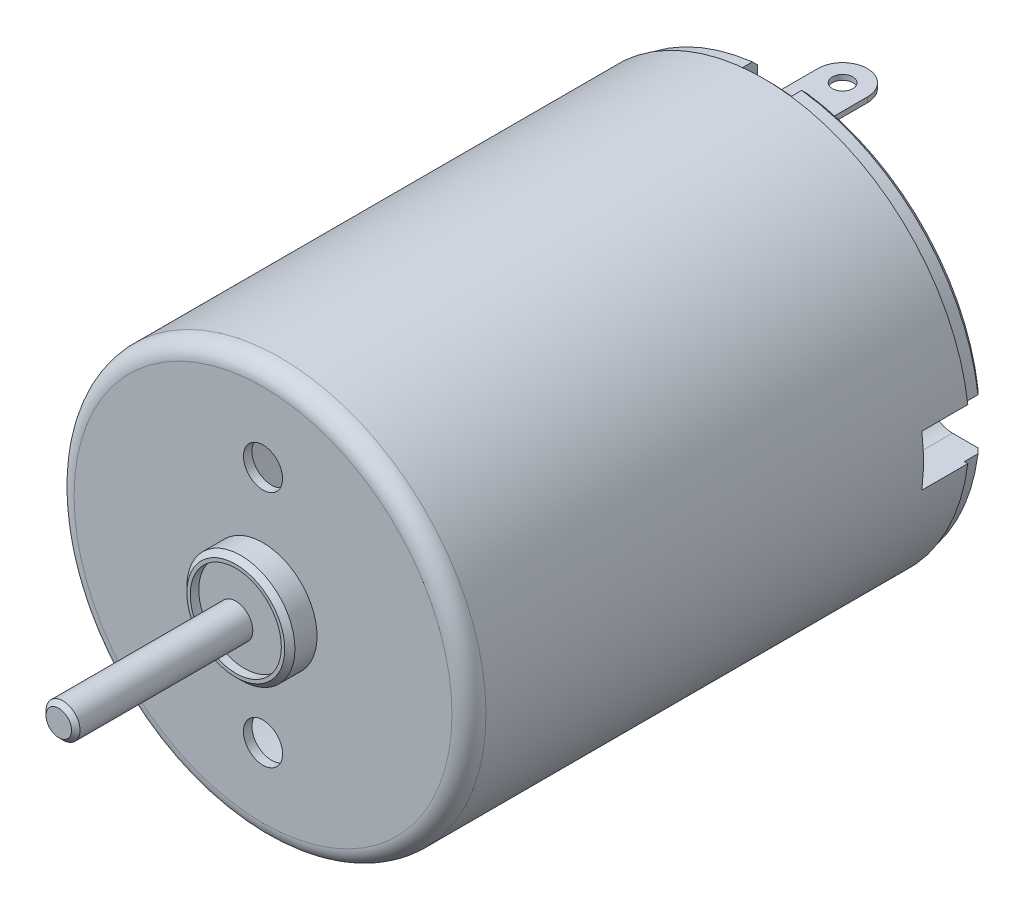
SolidWorks part; units mm, degrees
ref_plane "Front Plane" through (0, 0, 0) normal (0, 0, 1) x (1, 0, 0)
ref_plane "Top Plane" through (0, 0, 0) normal (0, 1, 0) x (1, 0, 0)
ref_plane "Right Plane" through (0, 0, 0) normal (1, 0, 0) x (0, 0, -1)
sketch "Sketch1" plane through (0, 0, 0) normal (0, 0, 1) x (1, 0, 0)
  circle A0 centre (0, 0) radius 12.1
  dimension "D1" = 24.2
extrude "Body" add sketch "Sketch1" along normal blind 30.5
sketch "Sketch2" plane through (0, 0, 30.5) normal (0, 0, 1) x (1, 0, 0)
  circle A0 centre (0, 0) radius 3.175
  dimension "D1" = 6.35
extrude "Boss-Extrude2" add sketch "Sketch2" along normal blind 1.6
sketch "Sketch3" plane through (0, 0, 32.1) normal (0, 0, 1) x (1, 0, 0)
  circle A0 centre (0, 0) radius 1
  dimension "D1" = 2
extrude "Shaft-front" add sketch "Sketch3" along normal offset from surface (10.4 mm away) 12 contours A0 up to face at (3.175, 0, 30.5) offset beyond the face yes
sketch "Sketch4" plane through (0, 0, 0) normal (0, 0, -1) x (-1, 0, 0)
  circle A0 centre (0, 0) radius 4.25
  dimension "D1" = 8.5
extrude "Boss-Extrude5" add sketch "Sketch4" along normal blind 2
sketch "Sketch5" plane through (0, 0, -2) normal (0, 0, -1) x (-1, 0, 0)
  circle A0 centre (0, 0) radius 1 construction
  circle A1 centre (0, 0) radius 1
extrude "Shaft-rear" add sketch "Sketch5" along normal offset from surface (0.5 mm away) 45 up to face at (1, 0, 42.5)
sketch "Sketch6" plane through (0, 0, 30.5) normal (0, 0, 1) x (1, 0, 0)
  line L0 (0, 7) -> (0, -7) construction
  circle A0 centre (0, 7) radius 1.15
  circle A1 centre (0, -7) radius 1.15
  dimension "D2" = 2.3
  dimension "D1" = 14
extrude "Cut-Extrude1" cut sketch "Sketch6" against normal offset from surface (28.5 mm away) 2 up to face at (-4.25, 0, 0)
sketch "Sketch7" plane through (0, 0, 0) normal (0, 0, -1) x (-1, 0, 0)
  line L0 (-6.45, 0) -> (6.45, 0) construction
  circle A0 centre (-6.45, 0) radius 1
  circle A1 centre (6.45, 0) radius 1
  dimension "D2" = 2
  dimension "D1" = 12.9
extrude "Cut-Extrude2" cut sketch "Sketch7" against normal offset from surface (28.5 mm away) 2 up to face at (1.15, 7, 30.5)
sketch "Sketch8" plane through (0, 0, -2) normal (0, 0, -1) x (-1, 0, 0)
  line L0 (3.75, 2) -> (3.75, -2)
  line L1 (-4.25, -5.1764) -> (-4.25, 5.307) construction
  circle A0 centre (0, 0) radius 4.25 construction
  circle A1 centre (0, 0) radius 4.25 construction
  arc A2 (3.75, -2) -> (3.75, 2) centre (0, 0) ccw
  dimension "D1" = 8
extrude "Cut-Extrude3" cut sketch "Sketch8" against normal up to surface (2 mm away) up to face at (5.45, 0, 0)
sketch "Sketch9" plane through (0, 0, 0) normal (0, 0, -1) x (-1, 0, 0)
  circle A0 centre (0, 0) radius 12.1 construction
  circle A1 centre (0, 0) radius 12.1
  circle A2 centre (0, 0) radius 11.9
  dimension "D1" = 23.8
extrude "Cut-Extrude4" cut sketch "Sketch9" against normal blind 1.1
chamfer "Chamfer1" distance 0.25 angle 45 2 edges at (1, 0, -2.5) (1, 0, 42.5)
sketch "Sketch10" plane through (0, 0, 0) normal (0, 0, -1) x (-1, 0, 0)
  line L0 (7.8477, -1.9) -> (4.9477, -1.9)
  line L2 (-1.45, -7.9432) -> (-1.45, -11.8113)
  line L4 (1.45, -7.9432) -> (1.45, -11.8113)
  line L5 (-4.9477, -1.9) -> (-7.8477, -1.9)
  line L6 (0, 0) -> (0, -12.9818) construction
  arc A0 (-7.8477, -1.9) -> (-1.45, -7.9432) centre (0, 0) ccw
  circle A1 centre (0, 0) radius 11.9
  circle A2 centre (0, 0) radius 11.9
  arc A3 (-4.9477, -1.9) -> (4.9477, -1.9) centre (0, 0) ccw
  arc A4 (1.45, -7.9432) -> (7.8477, -1.9) centre (0, 0) ccw
  circle M11 centre (0, 0) radius 11.9
  dimension "D3" = 2.9
  dimension "D4" = 5.3
  dimension "D2" = 2.9
  dimension "D5" = 1.9
  dimension "D1" = 0
extrude "Cut-Extrude5" cut sketch "Sketch10" against normal blind 0.9 contours L6 A3 L5 A0 L2 M11 | A3 L6 A2 L4 A4 L0 region at (-3.2233, -5.9985, 0) region at (3.2233, -5.9985, 0)
chamfer "Chamfer2" distance 0.3 angle 45 4 edges at (3.175, 0, 32.1) (-3.75, 0, -2) (4.25, 0, -2) (0, 11.9, 0)
fillet "Fillet1" radius 1 1 edges at (12.1, 0, 30.5)
mirror "Mirror1" about plane through (0, 0, 0) normal (0, 1, 0) of "Cut-Extrude5"
sketch "Sketch11" plane through (0, 0, 0) normal (0, 0, -1) x (-1, 0, 0)
  line L0 (-12.1, 0) -> (-10.0067, 0) construction
  line L1 (-12.0067, 1.5) -> (-10.0067, 1.5)
  line L2 (-12.0067, -1.5) -> (-10.0067, -1.5)
  circle A0 centre (0, 0) radius 12.1 construction
  arc A1 (-12.0067, 1.5) -> (-12.0067, -1.5) centre (0, 0) ccw
  arc A3 (-10.0067, -1.5) -> (-10.0067, 1.5) centre (-10.0067, 0) ccw
  dimension "D1" = 3
  dimension "D2" = 2
extrude "Cut-Extrude6" cut sketch "Sketch11" against normal blind 3.8
mirror "Mirror2" about plane through (0, 0, 0) normal (1, 0, 0) of "Cut-Extrude6"
sketch "Sketch12" plane through (0, 0, 0.9) normal (0, 0, -1) x (-1, 0, 0)
  line L0 (-1.45, -7.9432) -> (-1.45, -11.509) construction
  line L1 (-1.45, -9.25) -> (1.45, -9.25)
  line L2 (-1.45, -9.25) -> (-1.45, -9.55)
  line L3 (-1.45, -9.55) -> (1.45, -9.55)
  line L4 (1.45, -9.25) -> (1.45, -9.55)
  line L5 (1.45, -7.9432) -> (1.45, -11.509) construction
  line L6 (0, 0) -> (-16.807, 0) construction
  dimension "D1" = 18.5
  dimension "D2" = 0.3
extrude "Connector 1" add sketch "Sketch12" along normal offset from surface (5.9 mm away) 5 up to face at (5.45, 0, 0) offset beyond the face yes
fillet "Fillet2" 2 edges at (1.45, -9.4, -5) (-1.45, -9.4, -5) type full round first side face at (1.45, -9.4, -2.5) second side face at (-1.45, -9.4, -2.5) middle face at (0, -9.4, -5)
sketch "Sketch13" plane through (0, -9.25, 0) normal (0, 1, 0) x (1, 0, 0)
  circle A0 centre (0, 3.55) radius 0.6
  dimension "D1" = 1.2
extrude "Cut-Extrude7" cut sketch "Sketch13" against normal through all
mirror "Connector 2" about plane through (0, 0, 0) normal (0, 1, 0) of "Cut-Extrude7", "Fillet2", "Connector 1"
sketch "Sketch14" plane through (0, 0, 32.1) normal (0, 0, 1) x (1, 0, 0)
  circle A2 centre (0, 0) radius 2.675
  circle A3 centre (0, 0) radius 2.675
  dimension "D1" = 0.2
extrude "Cut-Extrude8" cut sketch "Sketch14" against normal blind 0.5
sketch "Sketch15" plane through (0, 0, 0) normal (0, 1, 0) x (1, 0, 0)
  line L9 (0, 0) -> (0, -50.2804) construction
  line L10 (-11.6, -4.3) -> (0, -4.3)
  line L11 (0, -4.3) -> (0, -30)
  line L12 (-11.1, -30) -> (11.1, -30)
  line L13 (11.6, -29.5) -> (11.6, -3.8)
  line L14 (-11.6, -3.8) -> (-11.6, -29.5)
  line L15 (-11.1, -30) -> (0, -30)
  line L17 (-11.6, -4.3) -> (-11.6, -29.5)
  line L18 (-10.0067, -3.8) -> (-12.0067, -3.8) construction
  arc A8 (11.1, -30) -> (11.6, -29.5) centre (11.1, -29.5) ccw
  arc A9 (-11.6, -29.5) -> (-11.1, -30) centre (-11.1, -29.5) ccw
  arc A11 (-11.6, -29.5) -> (-11.1, -30) centre (-11.1, -29.5) ccw
  dimension "D2" = 0.5
  dimension "D1" = 0.5
revolve "Cut-Revolve1" cut sketch "Sketch15" angle 360 about L9
